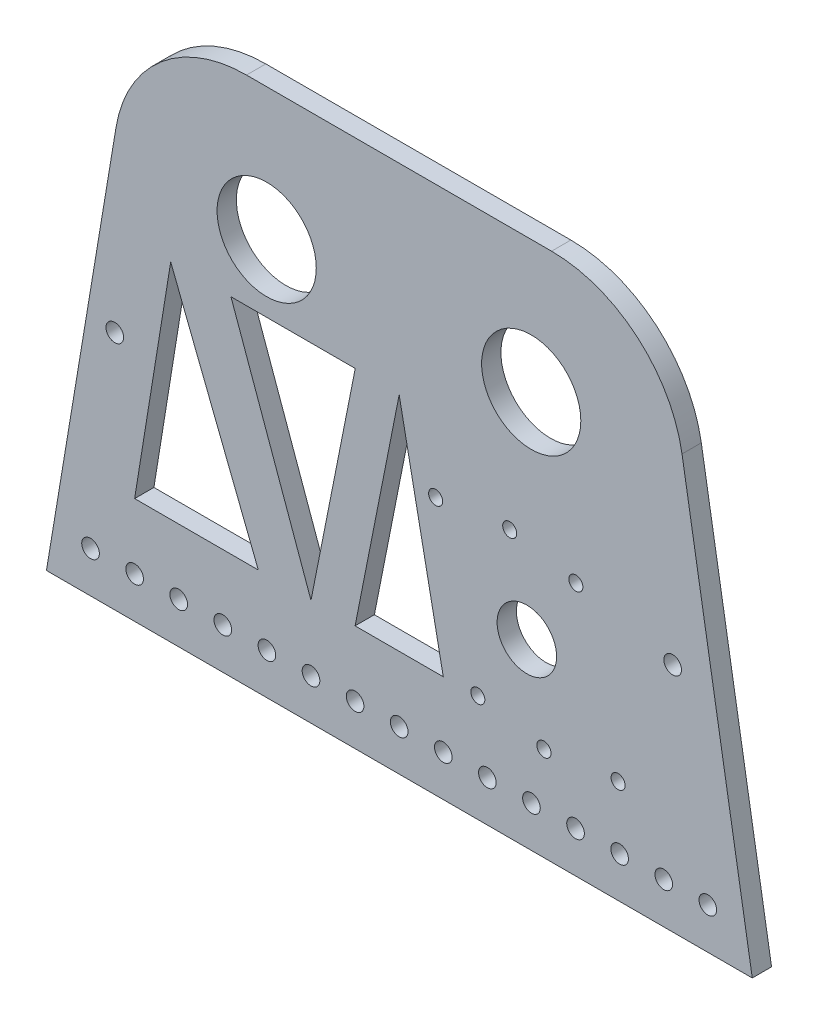
SolidWorks part; units mm, degrees
ref_plane "Front Plane" through (0, 0, 0) normal (0, 0, 1) x (1, 0, 0)
ref_plane "Top Plane" through (0, 0, 0) normal (0, 1, 0) x (1, 0, 0)
ref_plane "Right Plane" through (0, 0, 0) normal (1, 0, 0) x (0, 0, -1)
sketch "Sketch2" plane through (0, 0, 0) normal (0, 0, 1) x (1, 0, 0)
  line L0 (-33.222, -123.0337) -> (-58.5557, -123.0337)
  line L1 (-33.222, 29.3663) -> (119.178, 29.3663)
  line L3 (-33.222, -123.0337) -> (119.178, -123.0337)
  line L5 (-58.5557, -123.0337) -> (-33.222, 29.3663)
  line L6 (119.178, -123.0337) -> (144.7459, -123.0337)
  line L7 (144.7459, -123.0337) -> (119.178, 29.3663)
  line L8 (-22.7678, -28.1678) -> (-33.1557, -92.3946)
  line L9 (-33.1557, -92.3946) -> (2.468, -92.3946)
  line L10 (2.468, -92.3946) -> (-22.7678, -28.1678)
  line L14 (43.0443, -28.3997) -> (55.7443, -92.3946)
  line L15 (55.7443, -92.3946) -> (30.3443, -92.3946)
  line L16 (30.3443, -92.3946) -> (43.0443, -28.3997)
  line L20 (17.6443, -92.3946) -> (30.3903, -28.1678)
  line L21 (30.3903, -28.1678) -> (-5.4154, -28.1678)
  line L22 (-5.4154, -28.1678) -> (17.6443, -92.3946)
  circle A0 centre (4.878, -8.7337) radius 14.2875
  circle A1 centre (81.078, -8.7337) radius 14.2875
  circle A2 centre (-45.8557, -111.1877) radius 2.54
  circle A3 centre (-33.1557, -111.1877) radius 2.54
  circle A4 centre (-20.4557, -111.1877) radius 2.54
  circle A5 centre (-7.7557, -111.1877) radius 2.54
  circle A6 centre (4.9443, -111.1877) radius 2.54
  circle A7 centre (17.6443, -111.1877) radius 2.54
  circle A8 centre (30.3443, -111.1877) radius 2.54
  circle A9 centre (43.0443, -111.1877) radius 2.54
  circle A10 centre (55.7443, -111.1877) radius 2.54
  circle A11 centre (68.4443, -111.1877) radius 2.54
  circle A12 centre (81.1443, -111.1877) radius 2.54
  circle A13 centre (93.8443, -111.1877) radius 2.54
  circle A14 centre (106.5443, -111.1877) radius 2.54
  circle A15 centre (119.2443, -111.1877) radius 2.54
  circle A16 centre (131.9443, -111.1877) radius 2.54
  circle A17 centre (106.0951, -93.3478) radius 2.0193
  circle A18 centre (53.5442, -48.7401) radius 2.0193
  circle A19 centre (84.7428, -95.9685) radius 2.0429
  circle A20 centre (65.6988, -92.1571) radius 2.0193
  circle A21 centre (74.8753, -46.1298) radius 2.0193
  circle A22 centre (93.9404, -49.9309) radius 2.0193
  circle A23 centre (79.8188, -71.0396) radius 8.5708
  circle A24 centre (-38.8648, -53.8184) radius 2.54
  circle A25 centre (121.8199, -56.3584) radius 2.54
  dimension "D3" = 28.575
  dimension "D4" = 28.575
  dimension "D9" = 15
  dimension "D10" = 12.7
  dimension "D1" = 152.4
  dimension "D2" = 152.4
  dimension "D5" = 76.2
  dimension "D6" = 38.1
  dimension "D7" = 38.1
  dimension "D8" = 38.1
extrude "Boss-Extrude1" add sketch "Sketch2" along normal blind 5.5562
fillet "Fillet1" radius 38.1 2 edges at (-33.222, 29.3663, 2.7781) (119.178, 29.3663, 2.7781)
